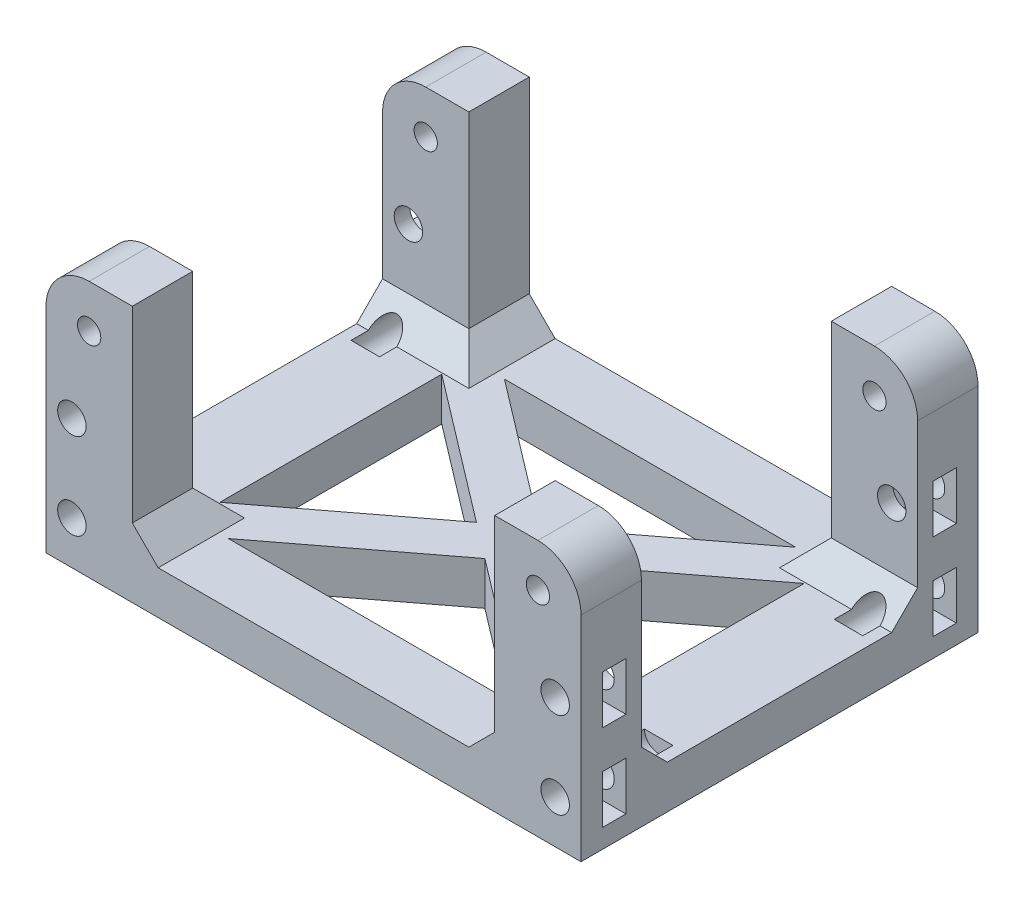
SolidWorks part; units mm, degrees
ref_plane "前视基准面" through (0, 0, 0) normal (0, 0, 1) x (1, 0, 0)
ref_plane "上视基准面" through (0, 0, 0) normal (0, 1, 0) x (1, 0, 0)
ref_plane "右视基准面" through (0, 0, 0) normal (1, 0, 0) x (0, 0, -1)
sketch "草图1" plane through (0, 0, 0) normal (0, 1, 0) x (1, 0, 0)
  line L1 (-31, -23) -> (31, -23)
  line L2 (-31, -23) -> (-31, 23)
  line L3 (-31, 23) -> (31, 23)
  line L4 (31, -23) -> (31, 23)
  line L5 (-31, -23) -> (31, 23) construction
  line L6 (-31, 23) -> (31, -23) construction
  point P0 (0, 0)
  dimension "D1" = 62
  dimension "D2" = 46
extrude "凸台-拉伸1" add sketch "草图1" along normal blind 5
sketch "草图2" plane through (0, 0, 23) normal (0, 0, 1) x (1, 0, 0)
  line L1 (-31, 5) -> (-21, 5)
  line L2 (-31, 5) -> (-31, 20)
  line L3 (-31, 20) -> (-21, 20)
  line L4 (-21, 5) -> (-21, 20)
  line L5 (31, 5) -> (21, 5)
  line L6 (31, 5) -> (31, 20)
  line L7 (31, 20) -> (21, 20)
  line L8 (21, 5) -> (21, 20)
  dimension "D1" = 15
  dimension "D2" = 10
extrude "凸台-拉伸2" add sketch "草图2" against normal blind 7
sketch "草图3" plane through (0, 0, 23) normal (0, 0, 1) x (1, 0, 0)
  line L0 (-31, 20) -> (31, 0) construction
  line L2 (-28, 5) -> (28, 5) construction
  line L3 (-28, 5) -> (-28, 15) construction
  line L4 (-28, 15) -> (28, 15) construction
  line L5 (28, 5) -> (28, 15) construction
  line L6 (-28, 5) -> (28, 15) construction
  line L7 (-28, 15) -> (28, 5) construction
  circle A0 centre (-28, 15) radius 1.65
  circle A1 centre (-28, 5) radius 1.65
  circle A2 centre (28, 5) radius 1.65
  circle A3 centre (28, 15) radius 1.65
  point P4 (0, 10)
  dimension "D3" = 3.3
  dimension "D1" = 10
  dimension "D2" = 56
extrude "切除-拉伸1" cut sketch "草图3" against normal blind 12
sketch "草图7" plane through (0, 20, 0) normal (0, 1, 0) x (1, 0, 0)
  line L1 (-31, -23) -> (-21, -23)
  line L2 (-31, -23) -> (-31, -16)
  line L3 (-31, -16) -> (-21, -16)
  line L4 (-21, -23) -> (-21, -16)
  line L5 (21, -23) -> (31, -23)
  line L6 (21, -23) -> (21, -16)
  line L7 (21, -16) -> (31, -16)
  line L8 (31, -23) -> (31, -16)
  point P12 (31, -16)
  point P14 (-21, -16)
extrude "凸台-拉伸4" add sketch "草图7" along normal blind 9.75
sketch "草图8" plane through (0, 0, 23) normal (0, 0, 1) x (1, 0, 0)
  line L0 (-26, 29.75) -> (-26, 24.75) construction
  line L1 (-31, 29.75) -> (-21, 29.75) construction
  line L2 (26, 29.75) -> (26, 24.75) construction
  line L3 (21, 29.75) -> (31, 29.75) construction
  line L4 (-26, 24.75) -> (26, 24.75) construction
  circle A0 centre (-26, 24.75) radius 1.35
  circle A1 centre (26, 24.75) radius 1.35
  dimension "D2" = 2.7
  dimension "D1" = 5
extrude "切除-拉伸4" cut sketch "草图8" against normal up to next
ref_plane "基准面1" through (0, 0, 20.5) normal (0, 0, 1) x (1, 0, 0)
sketch "草图4" plane through (0, 0, 20.5) normal (0, 0, 1) x (1, 0, 0)
  line L0 (-29.6166, 17.8) -> (-31.2332, 17.8)
  line L1 (-24.7668, 15) -> (-26.3834, 17.8)
  line L2 (-26.3834, 17.8) -> (-29.6166, 17.8)
  line L3 (-29.6166, 17.8) -> (-31.2332, 15) construction
  line L4 (-31.2332, 15) -> (-29.6166, 12.2) construction
  line L5 (-29.6166, 12.2) -> (-26.3834, 12.2)
  line L6 (-26.3834, 12.2) -> (-24.7668, 15)
  line L7 (-24.7668, 5) -> (-26.3834, 7.8)
  line L8 (-26.3834, 7.8) -> (-29.6166, 7.8)
  line L9 (-29.6166, 7.8) -> (-31.2332, 5) construction
  line L10 (-31.2332, 5) -> (-29.6166, 2.2) construction
  line L11 (-29.6166, 2.2) -> (-26.3834, 2.2)
  line L12 (-26.3834, 2.2) -> (-24.7668, 5)
  line L13 (24.7668, 15) -> (26.3834, 12.2)
  line L14 (26.3834, 12.2) -> (29.6166, 12.2)
  line L15 (29.6166, 12.2) -> (31.2332, 15) construction
  line L16 (31.2332, 15) -> (29.6166, 17.8) construction
  line L17 (29.6166, 17.8) -> (26.3834, 17.8)
  line L18 (26.3834, 17.8) -> (24.7668, 15)
  line L19 (24.7668, 5) -> (26.3834, 2.2)
  line L20 (26.3834, 2.2) -> (29.6166, 2.2)
  line L21 (29.6166, 2.2) -> (31.2332, 5) construction
  line L22 (31.2332, 5) -> (29.6166, 7.8) construction
  line L23 (29.6166, 7.8) -> (26.3834, 7.8)
  line L24 (26.3834, 7.8) -> (24.7668, 5)
  line L25 (-31.2332, 17.8) -> (-31.2332, 15)
  line L26 (-29.6166, 12.2) -> (-31.2332, 12.2)
  line L27 (-31.2332, 12.2) -> (-31.2332, 15)
  line L28 (-29.6166, 7.8) -> (-31.2332, 7.8)
  line L29 (-31.2332, 7.8) -> (-31.2332, 5)
  line L30 (-29.6166, 2.2) -> (-31.2332, 2.2)
  line L31 (-31.2332, 2.2) -> (-31.2332, 5)
  line L32 (29.6166, 17.8) -> (31.2332, 17.8)
  line L33 (31.2332, 17.8) -> (31.2332, 15)
  line L34 (29.6166, 12.2) -> (31.2332, 12.2)
  line L35 (31.2332, 12.2) -> (31.2332, 15)
  line L36 (29.6166, 7.8) -> (31.2332, 7.8)
  line L37 (31.2332, 7.8) -> (31.2332, 5)
  line L38 (31.2332, 5) -> (31.2332, 2.2)
  line L39 (31.2332, 2.2) -> (29.6166, 2.2)
  circle A0 centre (-28, 15) radius 2.8 construction
  circle A1 centre (-28, 5) radius 2.8 construction
  circle A2 centre (28, 15) radius 2.8 construction
  circle A3 centre (28, 5) radius 2.8 construction
  dimension "D1" = 5.6
extrude "切除-拉伸2" cut sketch "草图4" against normal blind 2.7
mirror "镜向1" about plane through (0, 0, 0) normal (0, 0, 1) of "切除-拉伸4", "凸台-拉伸2", "切除-拉伸1", "切除-拉伸2", "凸台-拉伸4"
sketch "草图5" plane through (0, 29.75, 0) normal (0, 1, 0) x (1, 0, 0)
  line L1 (-21, -16) -> (21, -16)
  line L2 (-21, -16) -> (-21, 16)
  line L3 (-21, 16) -> (21, 16)
  line L4 (21, -16) -> (21, 16)
  point P5 (18.4483, 13.6684)
  point P6 (21, 16)
  point P7 (-21, -16)
extrude "切除-拉伸3" cut sketch "草图5" against normal up to next
sketch "草图6" plane through (0, 0, 0) normal (0, 1, 0) x (1, 0, 0)
  line L0 (19.4849, -17.9886) -> (-22.5151, 14.0114)
  line L1 (19.4849, -17.9886) -> (22.5151, -14.0114)
  line L2 (-22.5151, 14.0114) -> (-19.4849, 17.9886)
  line L3 (22.5151, -14.0114) -> (-19.4849, 17.9886)
  line L4 (-21, 16) -> (21, -16) construction
  line L5 (-1.5151, -1.9886) -> (1.5151, 1.9886) construction
  line L6 (-22.5151, -14.0114) -> (19.4849, 17.9886)
  line L7 (-22.5151, -14.0114) -> (-19.4849, -17.9886)
  line L8 (19.4849, 17.9886) -> (22.5151, 14.0114)
  line L9 (-19.4849, -17.9886) -> (22.5151, 14.0114)
  line L10 (21, 16) -> (-21, -16) construction
  line L11 (-1.5151, 1.9886) -> (1.5151, -1.9886) construction
  point P0 (21, 16)
  point P1 (0, 0)
  point P2 (0, 0)
  dimension "D1" = 5
extrude "凸台-拉伸3" add sketch "草图6" along normal up to surface (5 mm away) contours L0 L6 L3 L2 | L3 L9 L8 L6 | L0 L9 L3 L6 | L7 L9 L0 L6 | L9 L0 L1 L3 region at (11.514, 0, 8.8029) region at (-11.514, 0, 8.8029) region at (0, 0, 0) region at (-11.514, 0, -8.8029) region at (11.514, 0, -8.8029) up to face at (0, 5, -19.5)
chamfer "倒角4" distance 3 angle 45 8 edges at (-21, 5, 19.5) (21, 5, 19.5) (23.675, 5, -16) (21, 5, -19.5) (-23.675, 5, -16) (-21, 5, -19.5) (-23.675, 5, 16) (23.675, 5, 16)
fillet "圆角1" radius 5 4 edges at (31, 29.75, -19.5) (31, 29.75, 19.5) (-31, 29.75, 19.5) (-31, 29.75, -19.5)
